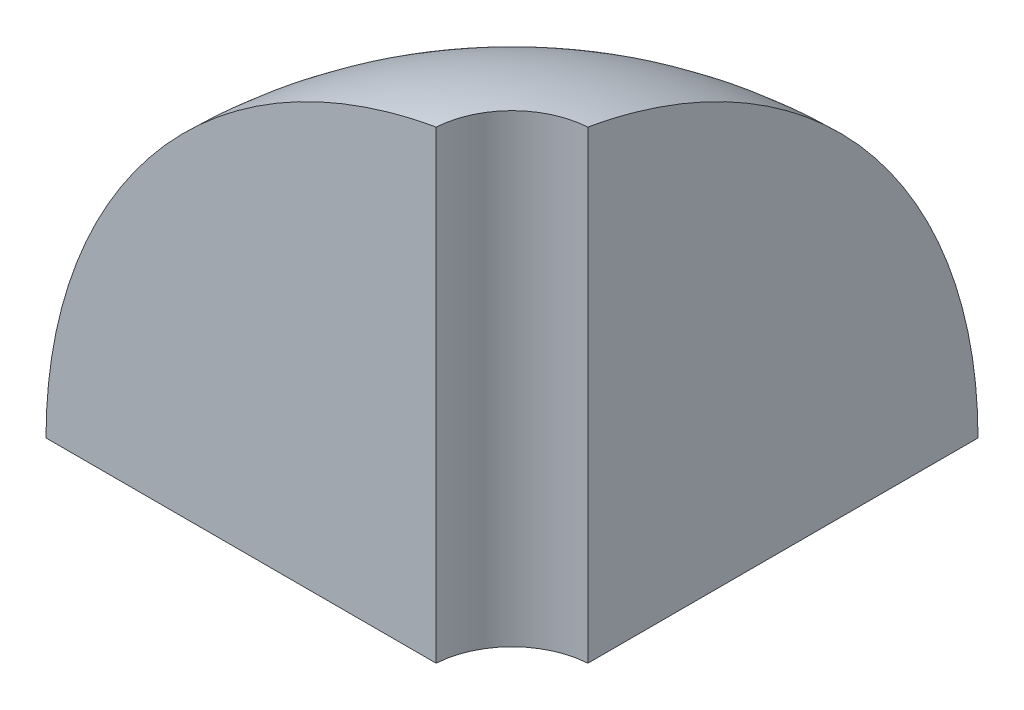
SolidWorks part; units mm, degrees
ref_plane "Front Plane" through (0, 0, 0) normal (0, 0, 1) x (1, 0, 0)
ref_plane "Top Plane" through (0, 0, 0) normal (0, 1, 0) x (1, 0, 0)
ref_plane "Right Plane" through (0, 0, 0) normal (1, 0, 0) x (0, 0, -1)
sketch "Sketch1" plane through (0, 0, 0) normal (0, 0, 1) x (1, 0, 0)
  line L0 (0, 44) -> (0, -44)
  arc A0 (0, 44) -> (0, -44) centre (0, 0) ccw
  dimension "D1" = 44
revolve "Revolve1" add sketch "Sketch1" angle 360 about L0
sketch "Sketch2" plane through (0, 0, 0) normal (0, 1, 0) x (1, 0, 0)
  line L0 (0, 16.8) -> (0, 0) construction
  line L1 (0, 0) -> (-16.8, 0) construction
  line L2 (-0.5, 43.9972) -> (-0.5, 0.5)
  line L3 (-0.5, 0.5) -> (-43.9972, 0.5)
  arc A2 (-43.9972, 0.5) -> (-0.5, 43.9972) centre (0, 0) ccw
  circle A3 centre (0, 0) radius 44 construction
  dimension "D1" = 0.5
  dimension "D2" = 0.5
extrude "Cut-Extrude1" cut sketch "Sketch2" against normal through all both and the other way through all
sketch "Sketch3" plane through (-0.5, 0, 0) normal (1, 0, 0) x (0, 0, -1)
  line L1 (0, 0) -> (43.9972, 0)
  line L2 (0, 0) -> (0, -43.9972)
  line L3 (0, -43.9972) -> (43.9972, -43.9972)
  line L4 (43.9972, 0) -> (43.9972, -43.9972)
  arc A0 (0.5, -43.9943) -> (0.5, 43.9943) centre (0, 0) ccw construction
extrude "Cut-Extrude2" cut sketch "Sketch3" against normal through all
sketch "Sketch6" plane through (0, 0, 0) normal (0, -1, 0) x (1, 0, 0)
  circle A0 centre (0, 0) radius 7.6
  dimension "D1" = 15.2
extrude "Cut-Extrude3" cut sketch "Sketch6" against normal through all
